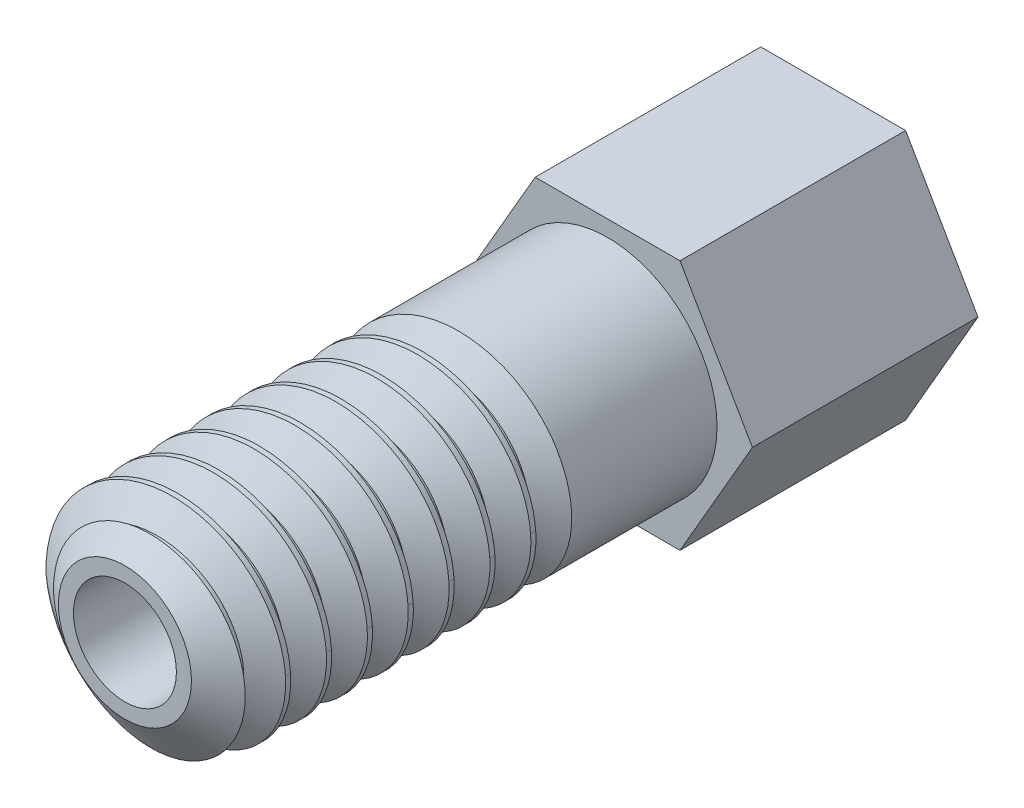
SolidWorks part; units mm, degrees
ref_plane "Front Plane" through (0, 0, 0) normal (0, 0, 1) x (1, 0, 0)
ref_plane "Top Plane" through (0, 0, 0) normal (0, 1, 0) x (1, 0, 0)
ref_plane "Right Plane" through (0, 0, 0) normal (1, 0, 0) x (0, 0, -1)
sketch "Sketch1" plane through (0, 0, 0) normal (0, 0, 1) x (1, 0, 0)
  circle A0 centre (0, 0) radius 1.7
  dimension "OD" = 3.4
extrude "Extrude1" add sketch "Sketch1" against normal blind 7.5
sketch "Sketch2" plane through (0, 0, 0) normal (0, 0, 1) x (1, 0, 0)
  circle A0 centre (0, 0) radius 1.7 construction
  circle A1 centre (0, 0) radius 1.7
curve "Helix/Spiral1" pitch 0.635 height 5.3975 radius 1.7 centre (0, 0, 0) axis (0, 0, -1) start towards (0, 1, 0) parameters "pitch"=0.635
sketch "Sketch3" plane through (0, 0, 0) normal (1, 0, 0) x (0, 0, -1)
  line L0 (-0.5556, 1.7) -> (-0.3175, 1.2876)
  line L1 (-0.3175, 1.2876) -> (-0.2381, 1.2876)
  line L2 (-0.2381, 1.2876) -> (0, 1.7)
  line L3 (-0.5556, 1.7) -> (0, 1.7)
  line L4 (-0.2778, 1.7) -> (-0.2778, 1.2876) construction
  line L5 (-0.4366, 1.4938) -> (-0.1191, 1.4938) construction
  line L6 (0, 1.7) -> (0, -1.7) construction
  dimension "D1" = 0.0794
  dimension "D2" = 0.3175
  dimension "D3" = 60
sweep "Cut-Sweep1" cut profiles "Sketch3" path "Helix/Spiral1"
sketch "Sketch4" plane through (0, 0, 0) normal (1, 0, 0) x (0, 0, -1)
  line L0 (0.4666, 1.7) -> (0, 1.0336)
  line L1 (0, 1.0336) -> (0, 1.7)
  line L2 (0.4666, 1.7) -> (0, 1.7)
  line L3 (-0.5556, 1.7) -> (0, 1.7) construction
  line L4 (0, 0) -> (7.0209, 0) construction
  dimension "D1" = 55
  dimension "D2" = 0.254
revolve "Cut-Revolve1" cut sketch "Sketch4" angle 360 about L4
sketch "Sketch6" plane through (0, 0, -7.5) normal (0, 0, -1) x (-1, 0, 0)
  line L1 (1.125, 1.9486) -> (-1.125, 1.9486)
  line L2 (-1.125, 1.9486) -> (-2.25, 0)
  line L3 (-2.25, 0) -> (-1.125, -1.9486)
  line L4 (-1.125, -1.9486) -> (1.125, -1.9486)
  line L5 (1.125, -1.9486) -> (2.25, 0)
  line L6 (2.25, 0) -> (1.125, 1.9486)
  circle A0 centre (0, 0) radius 1.9486 construction
  dimension "D1" = 4.5
extrude "Extrude2" add sketch "Sketch6" along normal blind 3.5052
sketch "Sketch11" plane through (0, 0, -11.0052) normal (0, 0, -1) x (-1, 0, 0)
  circle A0 centre (0, 0) radius 0.8
  dimension "D1" = 1.6
extrude "Cut-Extrude4" cut sketch "Sketch11" against normal through all
